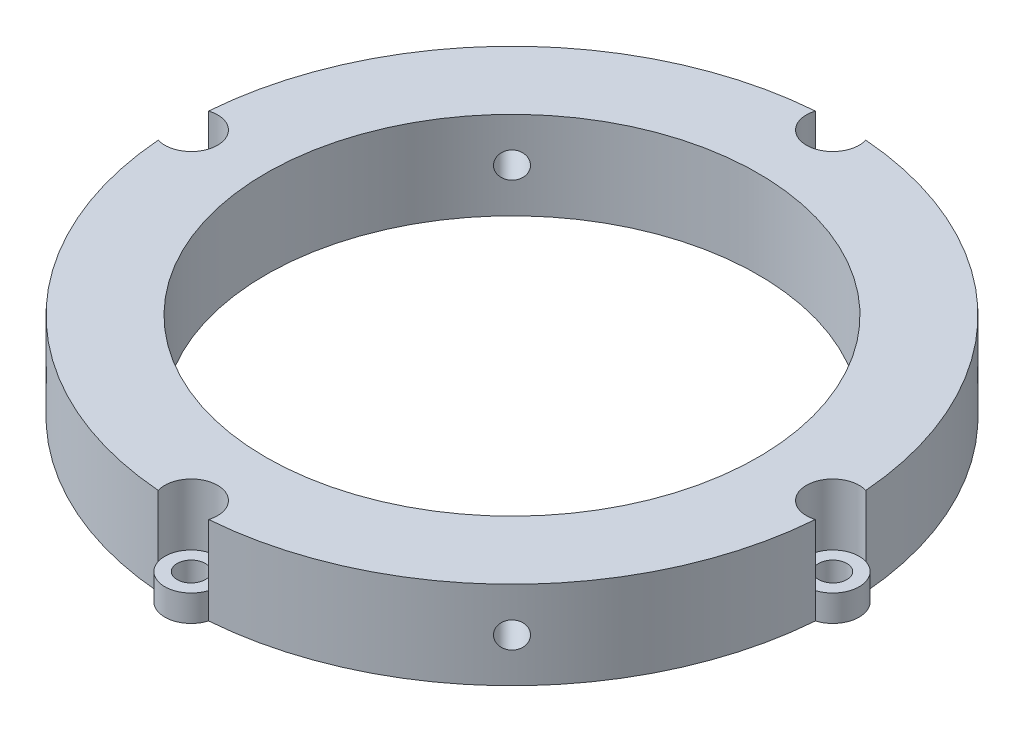
SolidWorks part; units mm, degrees
ref_plane "Ön Düzlem" through (0, 0, 0) normal (0, 0, 1) x (1, 0, 0)
ref_plane "Üst Düzlem" through (0, 0, 0) normal (0, 1, 0) x (1, 0, 0)
ref_plane "Sağ Düzlem" through (0, 0, 0) normal (1, 0, 0) x (0, 0, -1)
sketch "Çizim2" plane through (0, 0, 0) normal (0, 1, 0) x (1, 0, 0)
  arc A0 (-37.3801, -2.868) -> (-2.868, -37.3801) centre (0, 0) ccw
  circle A1 centre (0, 0) radius 28
  arc A2 (37.3801, 2.868) -> (37.3801, -2.868) centre (36.5, 0) ccw
  arc A4 (2.868, -37.3801) -> (-2.868, -37.3801) centre (0, -36.5) ccw
  arc A6 (-37.3801, -2.868) -> (-37.3801, 2.868) centre (-36.5, 0) ccw
  arc A8 (-2.868, 37.3801) -> (2.868, 37.3801) centre (0, 36.5) ccw
  arc A11 (2.868, -37.3801) -> (37.3801, -2.868) centre (0, 0) ccw
  arc A13 (37.3801, 2.868) -> (2.868, 37.3801) centre (0, 0) ccw
  arc A14 (-2.868, 37.3801) -> (-37.3801, 2.868) centre (0, 0) ccw
  point P19 (0, 0)
  dimension "D1" = 4
extrude "Yükseklik-Ekstrüzyon5" add sketch "Çizim2" along normal blind 10
ref_axis "Eksen1" through (0, 31.9173, 0) along (0, -1, 0)
ref_plane "Düzlem1" through (0, 0, 0) normal (-0.7071, 0, 0.7071) x (0, -1, 0)
sketch "Çizim3" plane through (0, 0, 0) normal (-0.7071, 0, 0.7071) x (0.7071, 0, 0.7071)
  circle A0 centre (0, 5) radius 1.49
extrude "Kes-Ekstrüzyon1" cut sketch "Çizim3" against normal through all
pattern_circular "Dairesel Kaplama1" count 4 over 360 about axis through (0, 31.9173, 0) along (0, -1, 0) of "Kes-Ekstrüzyon1"
sketch "Çizim4" plane through (0, 0, 0) normal (0, 1, 0) x (1, 0, 0)
  circle A0 centre (-36.5, 0) radius 3
  circle A1 centre (-36.5, 0) radius 1.6
extrude "Yükseklik-Ekstrüzyon6" add sketch "Çizim4" along normal blind 3
pattern_circular "Dairesel Kaplama2" count 4 over 360 about axis through (0, 31.9173, 0) along (0, -1, 0) of "Yükseklik-Ekstrüzyon6"
